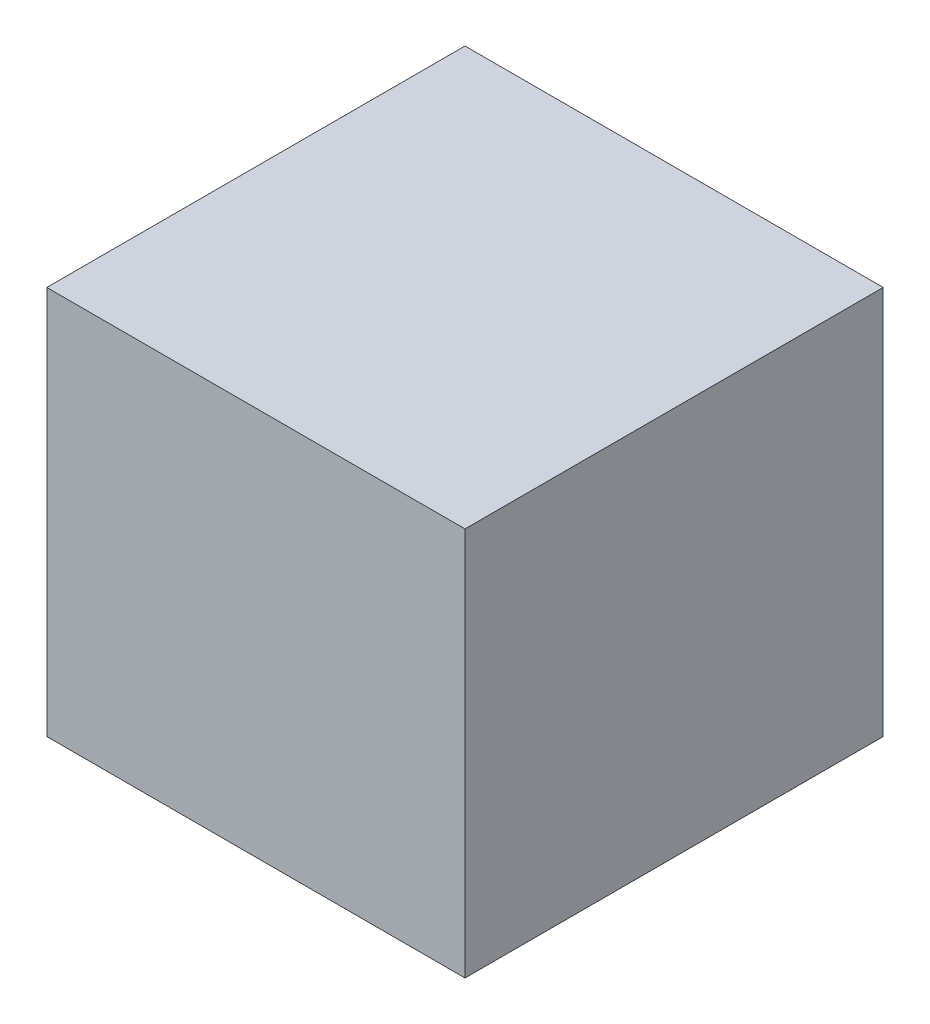
SolidWorks part; units mm, degrees
ref_plane "前视基准面" through (0, 0, 0) normal (0, 0, 1) x (1, 0, 0)
ref_plane "上视基准面" through (0, 0, 0) normal (0, 1, 0) x (1, 0, 0)
ref_plane "右视基准面" through (0, 0, 0) normal (1, 0, 0) x (0, 0, -1)
sketch "草图1" plane through (0, 0, 0) normal (0, 1, 0) x (1, 0, 0)
  line L1 (0, 0) -> (100, 0)
  line L2 (0, 0) -> (0, -100)
  line L3 (0, -100) -> (100, -100)
  line L4 (100, 0) -> (100, -100)
  line L5 (3, -97) -> (97, -97)
  line L6 (3, -97) -> (3, -3)
  line L7 (3, -3) -> (97, -3)
  line L8 (97, -97) -> (97, -3)
  dimension "D1" = 100
  dimension "D2" = 100
  dimension "D3" = 3
  dimension "D4" = 3
  dimension "D5" = 3
  dimension "D6" = 3
extrude "凸台-拉伸1" add sketch "草图1" along normal blind 3 contours L4 L3 L2 L1
extrude "凸台-拉伸2" add sketch "草图1<3>" against normal blind 90
sketch "草图1<3>" plane through (0, 0, 0) normal (0, 1, 0) x (1, 0, 0) same geometry as "草图1"
